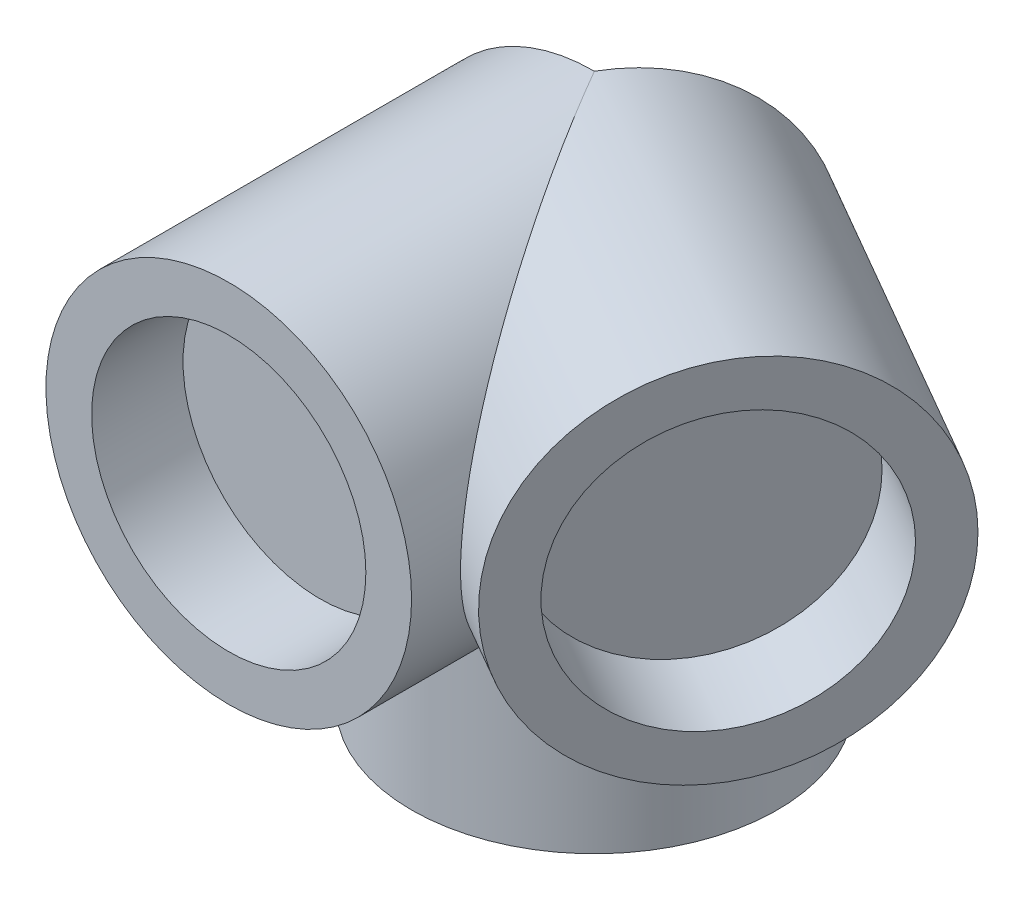
SolidWorks part; units mm, degrees
ref_plane "Front Plane" through (0, 0, 0) normal (0, 0, 1) x (1, 0, 0)
ref_plane "Top Plane" through (0, 0, 0) normal (0, 1, 0) x (1, 0, 0)
ref_plane "Right Plane" through (0, 0, 0) normal (1, 0, 0) x (0, 0, -1)
sketch "Sketch1" plane through (0, 0, 0) normal (0, 1, 0) x (1, 0, 0)
  circle A0 centre (0, 0) radius 10
  dimension "D1" = 20
extrude "Boss-Extrude1" add sketch "Sketch1" against normal blind 10
sketch "Sketch2" plane through (0, -10, 0) normal (0, -1, 0) x (1, 0, 0)
  circle A0 centre (0, 0) radius 7.5
  dimension "D1" = 15
extrude "Cut-Extrude1" cut sketch "Sketch2" against normal blind 5
sketch "Sketch3" plane through (0, 0, 0) normal (0, 1, 0) x (1, 0, 0)
  line L0 (0, 0) -> (0, -10)
  line L1 (0, 0) -> (-8.6603, -5)
  circle A0 centre (0, 0) radius 10 construction
  dimension "D1" = 60
ref_axis "Axis1" through (0, 0, 0) along (-0.866, 0, 0.5)
sketch "Sketch4" plane through (0, 0, 0) normal (1, 0, 0) x (0, 0, -1)
  line L0 (0, -10) -> (-10, -10)
  line L1 (-7.5, -10) -> (7.5, -10) construction
sketch "Sketch5" plane through (0, -10, 0) normal (0, -1, 0) x (1, 0, 0)
  line L0 (0, 0) -> (-8.6603, 5)
  line L1 (0, 0) -> (0, 10) construction
  circle A0 centre (0, 0) radius 10 construction
  dimension "D1" = 60
sketch "Sketch6" plane through (0, 0, 0) normal (1, 0, 0) x (0, 0, -1)
  line L0 (0, 0) -> (0, -10)
ref_plane "Plane1" through (0, 0, 0) normal (0.866, 0, 0.5) x (0, -1, 0)
sketch "Sketch7" plane through (0, 0, 0) normal (0.866, 0, 0.5) x (0, -1, 0)
  line L0 (0, 10) -> (0, -10) construction
  circle A0 centre (-10, 0) radius 10
  dimension "D2" = 20
  dimension "D1" = 10
extrude "Boss-Extrude2" add sketch "Sketch7" along normal blind 20 separate body
sketch "Sketch9" plane through (0, 0, 0) normal (0, 0, 1) x (1, 0, 0)
  line L0 (10, 0) -> (-10, 0) construction
  circle A0 centre (0, 10) radius 10
  dimension "D2" = 20
  dimension "D1" = 10
extrude "Boss-Extrude3" add sketch "Sketch9" along normal blind 20
sketch "Sketch10" plane through (0, 0, 20) normal (0, 0, 1) x (1, 0, 0)
  circle A0 centre (0, 10) radius 7.5
  dimension "D1" = 15
extrude "Cut-Extrude2" cut sketch "Sketch10" against normal blind 5
sketch "Sketch11" plane through (17.3205, 0, 10) normal (0.866, 0, 0.5) x (0.5, 0, -0.866)
  circle A0 centre (0, 10) radius 7.5
  dimension "D1" = 15
extrude "Cut-Extrude3" cut sketch "Sketch11" against normal blind 5
